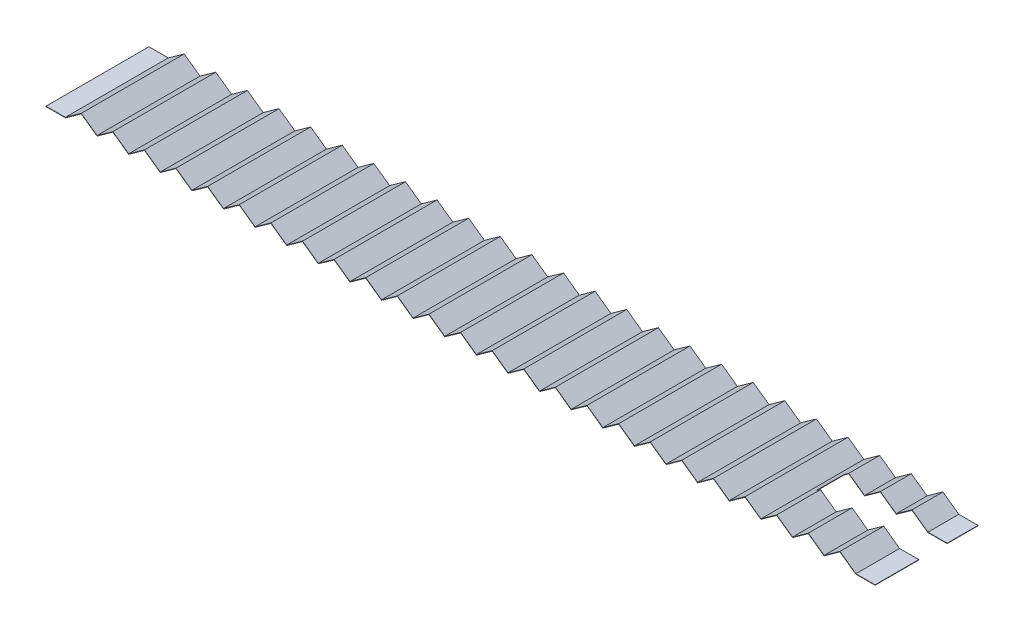
SolidWorks part; units mm, degrees
ref_plane "Front Plane" through (0, 0, 0) normal (0, 0, 1) x (1, 0, 0)
ref_plane "Top Plane" through (0, 0, 0) normal (0, 1, 0) x (1, 0, 0)
ref_plane "Right Plane" through (0, 0, 0) normal (1, 0, 0) x (0, 0, -1)
sketch "Sketch1" plane through (0, 0, 0) normal (0, 0, 1) x (1, 0, 0)
  line L0 (0, 0) -> (12.283, 8.7828)
  line L1 (12.283, 8.7828) -> (24.566, 0)
  line L2 (0, 0) -> (511, 0) construction
  line L3 (24.566, 0) -> (36.849, 8.7828)
  line L4 (36.849, 8.7828) -> (49.132, 0)
  line L5 (49.132, 0) -> (61.415, 8.7828)
  line L6 (61.415, 8.7828) -> (73.698, 0)
  line L7 (73.698, 0) -> (85.981, 8.7828)
  line L8 (85.981, 8.7828) -> (98.264, 0)
  line L9 (98.264, 0) -> (110.547, 8.7828)
  line L10 (110.547, 8.7828) -> (122.83, 0)
  line L11 (122.83, 0) -> (135.113, 8.7828)
  line L12 (135.113, 8.7828) -> (147.396, 0)
  line L13 (147.396, 0) -> (159.679, 8.7828)
  line L14 (159.679, 8.7828) -> (171.962, 0)
  line L15 (171.962, 0) -> (184.245, 8.7828)
  line L16 (184.245, 8.7828) -> (196.528, 0)
  line L17 (196.528, 0) -> (208.811, 8.7828)
  line L18 (208.811, 8.7828) -> (221.094, 0)
  line L19 (0, 0) -> (-15.1, 0)
  line L20 (221.094, 0) -> (233.377, 8.7828)
  line L21 (233.377, 8.7828) -> (245.66, 0)
  line L22 (245.66, 0) -> (257.943, 8.7828)
  line L23 (257.943, 8.7828) -> (270.226, 0)
  line L24 (270.226, 0) -> (282.509, 8.7828)
  line L25 (282.509, 8.7828) -> (294.792, 0)
  line L26 (294.792, 0) -> (307.075, 8.7828)
  line L27 (307.075, 8.7828) -> (319.358, 0)
  line L28 (319.358, 0) -> (331.641, 8.7828)
  line L29 (331.641, 8.7828) -> (343.924, 0)
  line L30 (343.924, 0) -> (356.207, 8.7828)
  line L31 (356.207, 8.7828) -> (368.49, 0)
  line L32 (368.49, 0) -> (380.773, 8.7828)
  line L33 (380.773, 8.7828) -> (393.056, 0)
  line L34 (393.056, 0) -> (405.339, 8.7828)
  line L35 (405.339, 8.7828) -> (417.622, 0)
  line L36 (417.622, 0) -> (429.905, 8.7828)
  line L37 (429.905, 8.7828) -> (442.188, 0)
  line L39 (442.188, 0) -> (454.471, 8.7828)
  line L40 (454.471, 8.7828) -> (466.754, 0)
  line L41 (466.754, 0) -> (479.037, 8.7828)
  line L42 (479.037, 8.7828) -> (491.32, 0)
  line L43 (491.32, 0) -> (503.603, 8.7828)
  line L44 (503.603, 8.7828) -> (515.886, 0)
  line L45 (515.886, 0) -> (528.169, 8.7828)
  line L46 (528.169, 8.7828) -> (540.452, 0)
  line L47 (540.452, 0) -> (552.735, 8.7828)
  line L48 (552.735, 8.7828) -> (565.018, 0)
  line L49 (565.018, 0) -> (577.301, 8.7828)
  line L50 (549.15, -119) -> (549.15, 187) construction
  line L51 (577.301, 8.7828) -> (589.584, 0)
  line L52 (589.584, 0) -> (601.867, 8.7828)
  line L53 (601.867, 8.7828) -> (614.15, 0)
  line L54 (614.15, 0) -> (629.15, 0)
  dimension "D1" = 511
  dimension "D2" = 15.1
  dimension "D3" = 15
  dimension "D4" = 24.566
  dimension "D6" = 80
  dimension "D5" = 25
extrude "Extrude-Thin1" add sketch "Sketch1" along normal mid plane 80 thin thin type one direction reverse wall 0.3
sketch "Sketch2" plane through (0, 0, 0) normal (0, 1, 0) x (1, 0, 0)
  line L1 (549.15, -6) -> (629.15, -6)
  line L2 (549.15, -6) -> (549.15, 16)
  line L3 (549.15, 16) -> (629.15, 16)
  line L4 (629.15, -6) -> (629.15, 16)
  line L5 (549.15, -6) -> (629.15, 16) construction
  line L6 (549.15, 16) -> (629.15, -6) construction
  line L8 (629.15, -40) -> (629.15, 40) construction
  point P0 (589.15, 5)
  dimension "D1" = 80
  dimension "D2" = 22
  dimension "D3" = 5
extrude "Cut-Extrude4" cut sketch "Sketch2" against normal through all and the other way through all contours L1 L4 L3 L2 region at (589.15, 0, -5)
